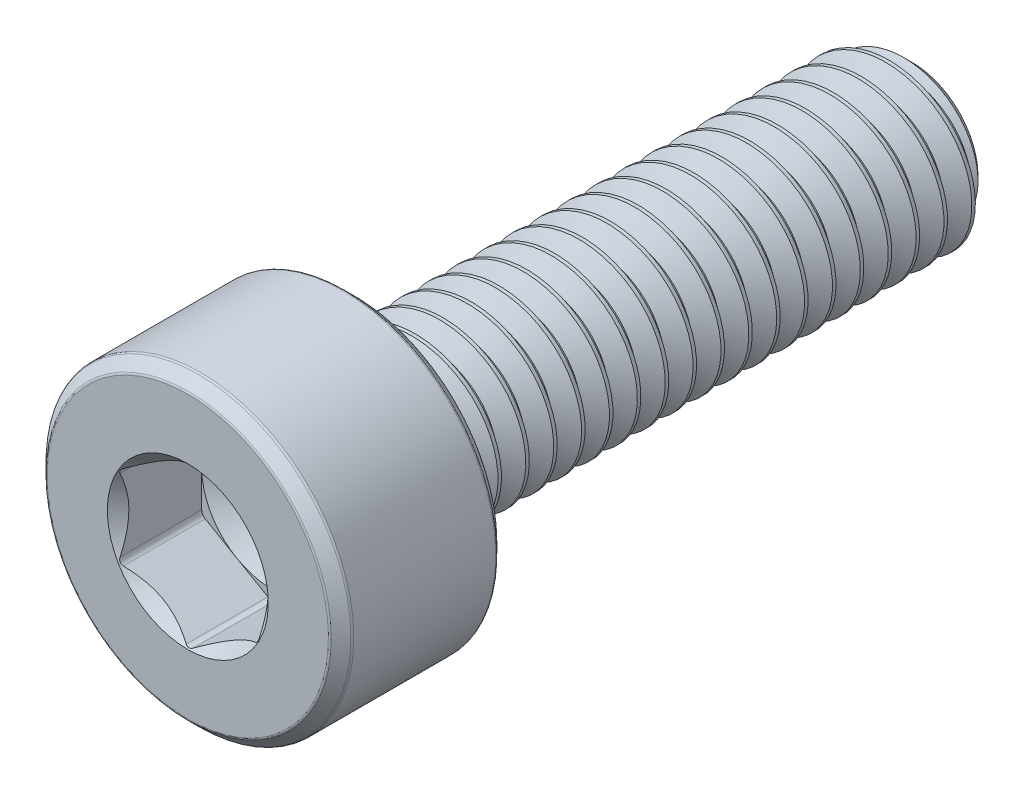
SolidWorks part; units mm, degrees
material "AISI 316 Stainless Steel Sheet (SS)"
ref_plane "Front Plane" through (0, 0, 0) normal (0, 0, 1) x (1, 0, 0)
ref_plane "Top Plane" through (0, 0, 0) normal (0, 1, 0) x (1, 0, 0)
ref_plane "Right Plane" through (0, 0, 0) normal (1, 0, 0) x (0, 0, -1)
sketch "Sketch1" plane through (0, 0, 0) normal (1, 0, 0) x (0, 0, -1)
  line L0 (-6.5, 0) -> (6.5, 0) construction
  line L1 (-6.5, 0) -> (-6.5, 2.75)
  line L2 (-6.5, 2.75) -> (-3.5, 2.75)
  line L3 (-3.5, 2.75) -> (-3.5, 1.5)
  line L4 (-3.5, 1.5) -> (6.1752, 1.5)
  line L5 (6.4687, 1.5541) -> (6.7187, 1.1211) construction
  line L6 (6.7187, 1.1211) -> (6.9687, 1.5541) construction
  line L7 (6.9687, 1.5541) -> (6.4687, 1.5541) construction
  line L8 (6.1752, 1.5) -> (6.5, 1.1752)
  line L9 (6.5, 1.1752) -> (6.5, 0)
  line L10 (6.5, 1.5) -> (6.9375, 1.5) construction
  line L11 (6.7187, 1.5541) -> (6.7187, 1.5) construction
  line L12 (6.7187, 1.5) -> (6.7187, 1.1752) construction
  line L13 (6.7187, 1.1752) -> (6.7187, 1.1211) construction
  line L14 (6.6875, 1.1752) -> (6.75, 1.1752)
  line L15 (6.4844, 1.5271) -> (6.9531, 1.5271)
  line L16 (6.75, 1.1752) -> (6.9531, 1.5271)
  line L17 (6.6875, 1.1752) -> (6.4844, 1.5271)
  line L18 (-6.5, 1.25) -> (-5, 1.25)
  line L19 (-5, 1.25) -> (-5, 0)
  line L20 (4.75, 1.5) -> (4.75, -1.5) construction
  point P20 (6.7187, 1.5271)
  point P22 (4.75, -1.5)
  point P28 (4.75, 0)
  point P29 (6.1752, -1.5)
  dimension "Head Diameter" = 5.5
  dimension "Length" = 10
  dimension "Head Height" = 3
  dimension "Thread Size" = 3
  dimension "D1" = 45
  dimension "Thread Pitch" = 0.5
  dimension "D3" = 0.0625
  dimension "Drive Size" = 2.5
  dimension "D4" = 1.75
  dimension "D5" = 1.5
sketch "Sketch3" plane through (0, 0, 0) normal (1, 0, 0) x (0, 0, -1)
  line L0 (-6.5, 2.5224) -> (-6.5, 1.25)
  line L1 (-6.5, 1.25) -> (-5, 1.25)
  line L2 (-5, 1.25) -> (-5, 0)
  line L3 (-5, 0) -> (6.5, 0)
  line L4 (6.5, 0) -> (6.5, 1.1752)
  line L5 (6.5, 1.1752) -> (6.1752, 1.5)
  line L6 (6.1752, 1.5) -> (-3.5, 1.5)
  line L7 (-3.5, 1.5) -> (-3.5, 2.5224)
  line L8 (-3.7276, 2.75) -> (-6.2724, 2.75)
  line L9 (-6.4849, 2.5589) -> (-6.3089, 2.7349)
  line L11 (-6.5, 2.75) -> (-3.5, 2.75) construction
  line L12 (-3.6911, 2.7349) -> (-3.5151, 2.5589)
  arc A5 (-3.5151, 2.5589) -> (-3.5, 2.5224) centre (-3.5516, 2.5224) cw
  arc A6 (-3.7276, 2.75) -> (-3.6911, 2.7349) centre (-3.7276, 2.6984) cw
  arc A7 (-6.2724, 2.75) -> (-6.3089, 2.7349) centre (-6.2724, 2.6984) ccw
  arc A8 (-6.5, 2.5224) -> (-6.4849, 2.5589) centre (-6.4484, 2.5224) cw
  point P17 (-5, 2.75)
  point P29 (-6.5, 2.5438)
  dimension "D3" = 0.0516
  dimension "D1" = 45
  dimension "D2" = 0.2062
revolve "Revolve1" add sketch "Sketch3" angle 360 about L0
sketch "Sketch4" plane through (0, 0, 6.5) normal (0, 0, 1) x (1, 0, 0)
  line L1 (0, 1.4434) -> (-1.25, 0.7217)
  line L2 (-1.25, 0.7217) -> (-1.25, -0.7217)
  line L3 (-1.25, -0.7217) -> (0, -1.4434)
  line L4 (0, -1.4434) -> (1.25, -0.7217)
  line L5 (1.25, -0.7217) -> (1.25, 0.7217)
  line L6 (1.25, 0.7217) -> (0, 1.4434)
  circle A0 centre (0, 0) radius 1.25 construction
extrude "Cut-Extrude1" cut sketch "Sketch4" against normal up to vertex (1.5 mm away) up to point (0, 1.25, 5)
sketch "Sketch5" plane through (0, 0, 6.5) normal (0, 0, 1) x (1, 0, 0)
  circle A0 centre (0, 0) radius 1.4434
extrude "Cut-Extrude2" cut sketch "Sketch5" against normal up to next (1.5 mm away) draft 45
sketch "Sketch10" plane through (0, 0, 5) normal (0, 0, 1) x (1, 0, 0)
  line L0 (1.25, 0.7217) -> (1.25, -0.7217) construction
  circle A0 centre (0, 0) radius 1.25
extrude "Cut-Extrude3" cut sketch "Sketch10" against normal through all draft 60
fillet "Fillet1" radius 0.125 6 edges at (-1.25, 0.7217, 5.75) (0, 1.4434, 5.75) (1.25, 0.7217, 5.75) (1.25, -0.7217, 5.75) (0, -1.4434, 5.75) (-1.25, -0.7217, 5.75)
sketch "Sketch6" plane through (0, 0, -6.5) normal (0, 0, -1) x (-1, 0, 0)
  circle A0 centre (0, 0) radius 1.5 construction
  circle A1 centre (0, 0) radius 1.5
curve "Helix/Spiral1" pitch 0.5 height 10.5 radius 1.5 centre (0, 0, -6.5) axis (0, 0, 1) start towards (0, 1, 0)
sketch "Sketch7" plane through (0, 0, 0) normal (1, 0, 0) x (0, 0, -1)
  line L0 (6.6875, 1.1752) -> (6.75, 1.1752) construction
  line L1 (6.6875, 1.1752) -> (6.4844, 1.5271) construction
  line L2 (6.4844, 1.5271) -> (6.9531, 1.5271) construction
  line L3 (6.75, 1.1752) -> (6.9531, 1.5271) construction
  line L4 (6.6875, 1.1752) -> (6.75, 1.1752)
  line L5 (6.6875, 1.1752) -> (6.4844, 1.5271)
  line L6 (6.4844, 1.5271) -> (6.9531, 1.5271)
  line L7 (6.75, 1.1752) -> (6.9531, 1.5271)
sweep "Cut-Sweep1" cut profiles "Sketch7" path "Helix/Spiral1" align with end faces yes
sketch "Sketch11" plane through (0, 0, 0) normal (1, 0, 0) x (0, 0, -1)
  line L0 (-3.5, 1.625) -> (-3.375, 1.5) construction
  line L1 (-3.5, 2.75) -> (-3.5, 1.5) construction
  line L2 (-3.5, 1.5) -> (6.1752, 1.5) construction
  line L3 (-3.375, 1.5) -> (-3.25, 1.5)
  line L4 (-3.25, 1.5) -> (-1.75, 0)
  line L5 (-6.5, 0) -> (6.5, 0) construction
  line L6 (-1.75, 0) -> (-3.5, 0)
  line L7 (-3.5, 0) -> (-3.5, 1.625) construction
  line L8 (-3.5, 1.625) -> (-4.2783, 1.625)
  line L9 (-4.2783, 1.625) -> (-4.2783, 0)
  line L10 (-4.2783, 0) -> (-3.5, 0)
  arc A0 (-3.375, 1.5) -> (-3.5, 1.625) centre (-3.375, 1.625) cw
  dimension "D1" = 45
  dimension "D2" = 0.125
  dimension "D3" = 45
  dimension "D4" = 0.25
revolve "Revolve2" add sketch "Sketch11" angle 360 about L6
equation "\"D3@Sketch1\" = \"Thread Pitch@Sketch1\" / 8"
equation "\"D4@Sketch1\" = \"Thread Pitch@Sketch1\" * 3.5"
equation "\"D3@Helix/Spiral1\" = \"Length@Sketch1\" + \"Thread Pitch@Sketch1\""
equation "\"D4@Helix/Spiral1\" = \"Thread Pitch@Sketch1\""
equation "\"D5@Sketch1\"=\"Head Height@Sketch1\"*0.5"
equation "\"D2@Sketch3\"=\"Head Diameter@Sketch1\" *0.0375"
equation "\"D2@Sketch11\"=\"Thread Pitch@Sketch1\" / 4"
equation "\"D4@Sketch11\"=\"Thread Pitch@Sketch1\"/2"
equation "\"D1@Fillet1\"=\"Drive Size@Sketch1\"*0.05"
equation "\"D1@Fillet1\" = \"Drive Size@Sketch1\" * 0.05"
equation "\"D3@Sketch3\"=\"D2@Sketch3\"*0.25"
